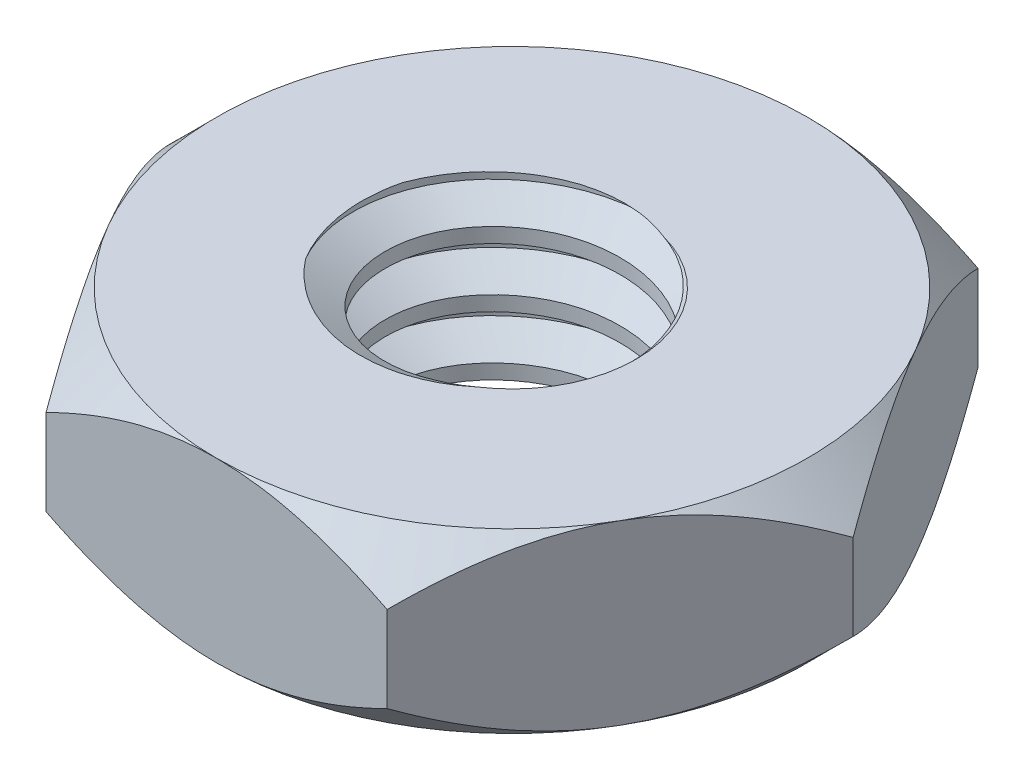
SolidWorks part; units mm, degrees
ref_plane "Front Plane" through (0, 0, 0) normal (0, 0, 1) x (1, 0, 0)
ref_plane "Top Plane" through (0, 0, 0) normal (0, 1, 0) x (1, 0, 0)
ref_plane "Right Plane" through (0, 0, 0) normal (1, 0, 0) x (0, 0, -1)
sketch "Sketch1" plane through (0, 0, 0) normal (0, 1, 0) x (1, 0, 0)
  line L1 (2.8868, 0) -> (1.4434, 2.5)
  line L2 (1.4434, 2.5) -> (-1.4434, 2.5)
  line L3 (-1.4434, 2.5) -> (-2.8868, 0)
  line L4 (-2.8868, 0) -> (-1.4434, -2.5)
  line L5 (-1.4434, -2.5) -> (1.4434, -2.5)
  line L6 (1.4434, -2.5) -> (2.8868, 0)
  circle A0 centre (0, 0) radius 2.5 construction
  dimension "D1" = 5
extrude "Boss-Extrude1" add sketch "Sketch1" along normal mid plane 1.5
sketch "Sketch2" plane through (0, 0.75, 0) normal (0, 1, 0) x (1, 0, 0)
  line L0 (1.4434, 2.5) -> (-1.4434, 2.5) construction
  circle A0 centre (0, 0) radius 2.5
extrude "Cut-Extrude1" cut sketch "Sketch2" against normal through all draft 45 flip side to cut
mirror "Mirror1" about plane through (0, 0, 0) normal (0, 1, 0) of "Cut-Extrude1"
sketch "Sketch3" plane through (0, 0.75, 0) normal (0, 1, 0) x (1, 0, 0)
  circle A0 centre (0, 0) radius 1
  dimension "D1" = 2
extrude "Cut-Extrude2" cut sketch "Sketch3" against normal through all
chamfer "Chamfer1" distance 0.05 angle 45 2 edges at (0, -0.75, 1) (0, 0.75, 1)
thread "Thread1" pitch 0.5 method cut profile "Thread Profile1" start angle 0, offset 1, length 0, pitch 0.5, diameter 2
ref_plane "Plane1" through (1, -1.7, 0) normal (0, 0, 1) x (1, 0, 0)
sketch "Thread Profile1" plane through (1, -1.7, 0) normal (0, 0, 1) x (1, 0, 0)
  line L0 (0, 0) -> (0, 0.5) construction
  line L1 (0, 0) -> (0.2706, 0.1562)
  line L2 (0.2706, 0.1562) -> (0.2706, 0.2187)
  line L3 (0.2706, 0.2187) -> (0, 0.375)
  line L4 (0.2706, 0.1875) -> (0, 0.1875) construction
  line L11 (0, 0) -> (0, 0.375)
  point P2 (0, 0)
  dimension "Pitch" = 0.5
  dimension "Profile_Angle" = 60
  dimension "Profile_Land" = 0.0625
  dimension "Profile_Height" = 0.2706
equation "\"Nut Head Dia\"= 5mm"
equation "\"Nut Head Thickness\"= 1.5mm"
equation "\"Nut hole Dia\"= 2mm"
equation "\"D1@Sketch1\"=\"Nut Head Dia\""
equation "\"D1@Boss-Extrude1\"=\"Nut Head Thickness\""
equation "\"D1@Sketch3\"=\"Nut hole Dia\""
